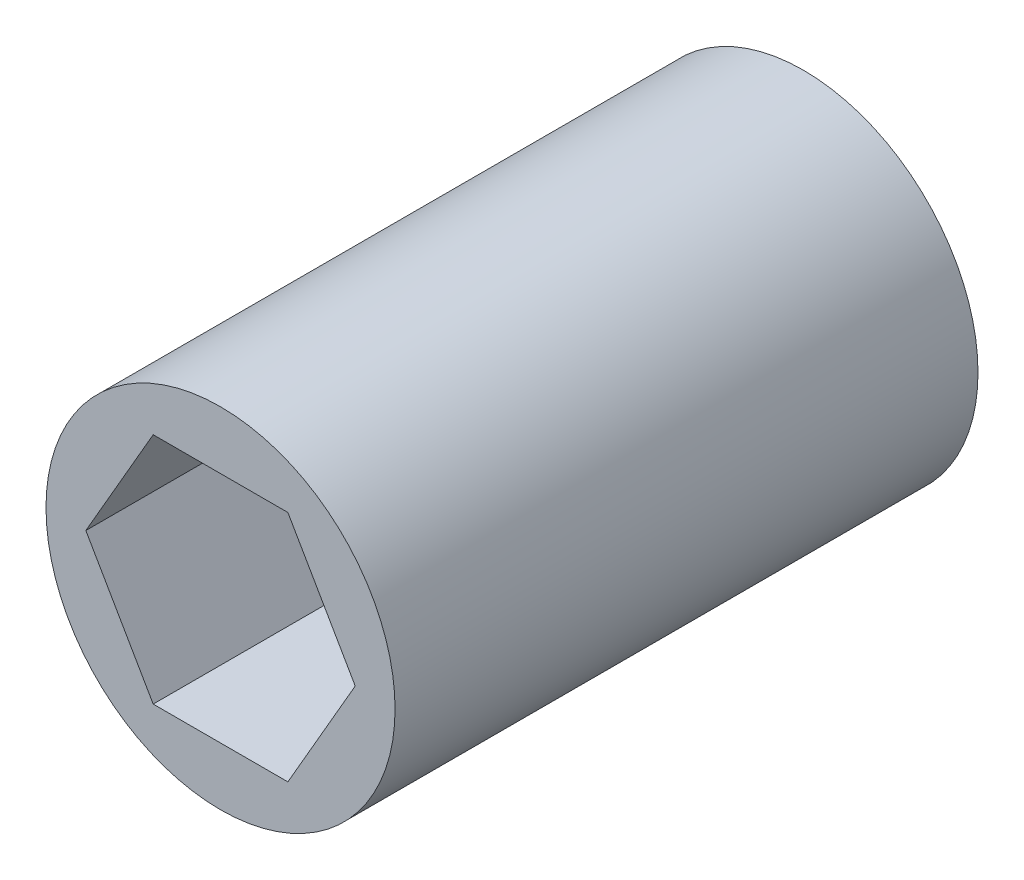
SolidWorks part; units mm, degrees
ref_plane "Front Plane" through (0, 0, 0) normal (0, 0, 1) x (1, 0, 0)
ref_plane "Top Plane" through (0, 0, 0) normal (0, 1, 0) x (1, 0, 0)
ref_plane "Right Plane" through (0, 0, 0) normal (1, 0, 0) x (0, 0, -1)
sketch "Sketch1" plane through (0, 0, 0) normal (0, 0, 1) x (1, 0, 0)
  line L1 (5.7879, 0) -> (2.894, 5.0125)
  line L2 (2.894, 5.0125) -> (-2.894, 5.0125)
  line L3 (-2.894, 5.0125) -> (-5.7879, 0)
  line L4 (-5.7879, 0) -> (-2.894, -5.0125)
  line L5 (-2.894, -5.0125) -> (2.894, -5.0125)
  line L6 (2.894, -5.0125) -> (5.7879, 0)
  circle A0 centre (0, 0) radius 7.5
  circle A1 centre (0, 0) radius 5.0125 construction
  dimension "D1" = 10.025
  dimension "D2" = 15
extrude "Boss-Extrude1" add sketch "Sketch1" along normal mid plane 25.05
ref_axis "Axis1" through (0, 0, 14.048) along (0, 0, -1)
